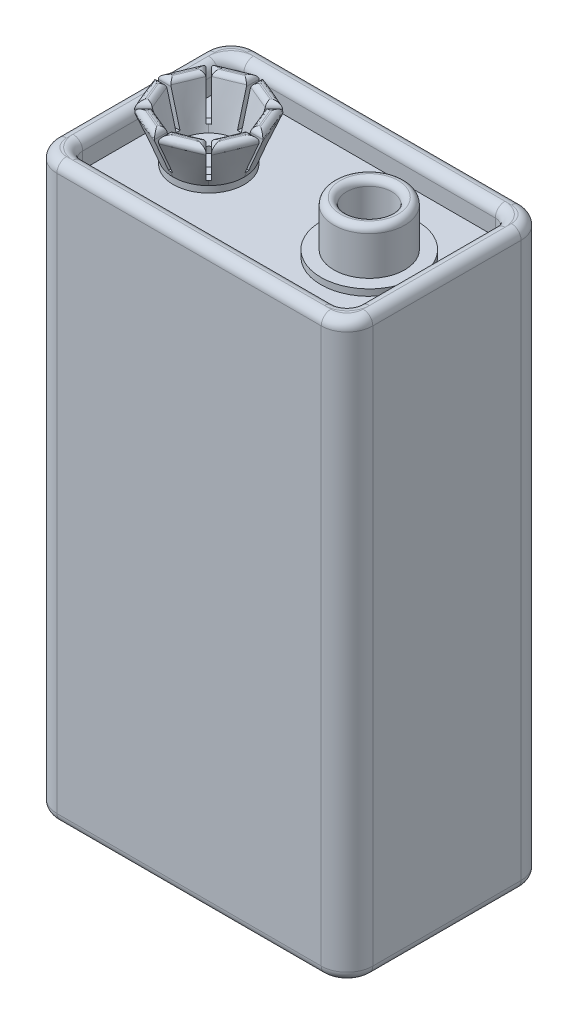
SolidWorks part; units mm, degrees
ref_plane "Front Plane" through (0, 0, 0) normal (0, 0, 1) x (1, 0, 0)
ref_plane "Top Plane" through (0, 0, 0) normal (0, 1, 0) x (1, 0, 0)
ref_plane "Right Plane" through (0, 0, 0) normal (1, 0, 0) x (0, 0, -1)
sketch "Sketch1" plane through (0, 0, 0) normal (0, 1, 0) x (1, 0, 0)
  line L1 (-10.25, -7.75) -> (10.25, -7.75)
  line L2 (-12.25, -5.75) -> (-12.25, 5.75)
  line L3 (-10.25, 7.75) -> (10.25, 7.75)
  line L4 (12.25, -5.75) -> (12.25, 5.75)
  line L5 (-12.25, -7.75) -> (12.25, 7.75) construction
  line L6 (-12.25, 7.75) -> (12.25, -7.75) construction
  arc A0 (10.25, -7.75) -> (12.25, -5.75) centre (10.25, -5.75) ccw
  arc A1 (-10.25, -7.75) -> (-12.25, -5.75) centre (-10.25, -5.75) cw
  arc A2 (10.25, 7.75) -> (12.25, 5.75) centre (10.25, 5.75) cw
  arc A3 (-12.25, 5.75) -> (-10.25, 7.75) centre (-10.25, 5.75) cw
  point P0 (0, 0)
  dimension "D3" = 2
  dimension "D1" = 24.5
  dimension "D2" = 15.5
extrude "Boss-Extrude1" add sketch "Sketch1" along normal blind 44.5
sketch "Sketch2" plane through (0, 0, 0) normal (0, -1, 0) x (-1, 0, 0)
  line L0 (10.25, -7.75) -> (-10.25, -7.75) construction
  line L1 (9.25, 6.25) -> (-9.25, 6.25)
  line L2 (10.75, 4.75) -> (10.75, -4.75)
  line L3 (9.25, -6.25) -> (-9.25, -6.25)
  line L4 (-10.75, 4.75) -> (-10.75, -4.75)
  line L5 (10.75, 6.25) -> (-10.75, -6.25) construction
  line L6 (10.75, -6.25) -> (-10.75, 6.25) construction
  line L7 (-12.25, -5.75) -> (-12.25, 5.75) construction
  arc A0 (-9.25, 6.25) -> (-10.75, 4.75) centre (-9.25, 4.75) ccw
  arc A1 (9.25, 6.25) -> (10.75, 4.75) centre (9.25, 4.75) cw
  arc A2 (-9.25, -6.25) -> (-10.75, -4.75) centre (-9.25, -4.75) cw
  arc A3 (10.75, -4.75) -> (9.25, -6.25) centre (9.25, -4.75) cw
  point P0 (0, 0)
  dimension "D3" = 1.5
  dimension "D1" = 1.5
  dimension "D2" = 1.5
extrude "Cut-Extrude1" cut sketch "Sketch2" against normal blind 2
fillet "Fillet1" radius 0.75 16 edges at (12.25, 0, 0) (11.6642, 0, -7.1642) (0, 0, -7.75) (-11.6642, 0, -7.1642) (-12.25, 0, 0) (-11.6642, 0, 7.1642) (0, 0, 7.75) (11.6642, 0, 7.1642) (10.3107, 0, 5.8107) (0, 0, 6.25) (-10.3107, 0, 5.8107) (-10.75, 0, 0) (-10.3107, 0, -5.8107) (0, 0, -6.25) (10.3107, 0, -5.8107) (10.75, 0, 0)
sketch "Sketch3" plane through (0, 2, 0) normal (0, -1, 0) x (-1, 0, 0)
  line L1 (9, 5.5) -> (-9, 5.5)
  line L2 (10, 4.5) -> (10, -4.5)
  line L3 (9, -5.5) -> (-9, -5.5)
  line L4 (-10, 4.5) -> (-10, -4.5)
  line L5 (10, 5.5) -> (-10, -5.5) construction
  line L6 (10, -5.5) -> (-10, 5.5) construction
  arc A0 (-9, 5.5) -> (-10, 4.5) centre (-9, 4.5) ccw
  arc A1 (9, 5.5) -> (10, 4.5) centre (9, 4.5) cw
  arc A2 (-9, -5.5) -> (-10, -4.5) centre (-9, -4.5) cw
  arc A3 (10, -4.5) -> (9, -5.5) centre (9, -4.5) cw
  point P0 (0, 0)
  dimension "D3" = 1
  dimension "D1" = 20
  dimension "D2" = 11
extrude "Boss-Extrude2" add sketch "Sketch3" along normal blind 1
fillet "Fillet2" radius 0.5 16 edges at (0, 1, -5.5) (-9.7071, 1, -5.2071) (-10, 1, 0) (-9.7071, 1, 5.2071) (0, 1, 5.5) (9.7071, 1, 5.2071) (10, 1, 0) (9.7071, 1, -5.2071) (-10, 2, 0) (-9.7071, 2, 5.2071) (0, 2, 5.5) (9.7071, 2, 5.2071) (10, 2, 0) (9.7071, 2, -5.2071) (0, 2, -5.5) (-9.7071, 2, -5.2071)
sketch "Sketch4" plane through (0, 44.5, 0) normal (0, 1, 0) x (1, 0, 0)
  line L1 (10.25, 7.75) -> (-10.25, 7.75) construction
  line L2 (-9.75, -6.25) -> (9.75, -6.25)
  line L3 (-10.75, -5.25) -> (-10.75, 5.25)
  line L4 (-9.75, 6.25) -> (9.75, 6.25)
  line L5 (10.75, -5.25) -> (10.75, 5.25)
  line L6 (-10.75, -6.25) -> (10.75, 6.25) construction
  line L8 (-10.75, 6.25) -> (10.75, -6.25) construction
  line L9 (12.25, -5.75) -> (12.25, 5.75) construction
  arc A0 (9.75, -6.25) -> (10.75, -5.25) centre (9.75, -5.25) ccw
  arc A1 (-9.75, -6.25) -> (-10.75, -5.25) centre (-9.75, -5.25) cw
  arc A2 (9.75, 6.25) -> (10.75, 5.25) centre (9.75, 5.25) cw
  arc A3 (-10.75, 5.25) -> (-9.75, 6.25) centre (-9.75, 5.25) cw
  point P0 (0, 0)
  dimension "D3" = 1
  dimension "D1" = 1.5
  dimension "D2" = 1.5
extrude "Cut-Extrude2" cut sketch "Sketch4" against normal blind 2
fillet "Fillet4" radius 0.75 16 edges at (0, 44.5, 7.75) (-11.6642, 44.5, 7.1642) (-12.25, 44.5, 0) (-11.6642, 44.5, -7.1642) (0, 44.5, -7.75) (11.6642, 44.5, -7.1642) (12.25, 44.5, 0) (11.6642, 44.5, 7.1642) (10.75, 44.5, 0) (10.4571, 44.5, -5.9571) (0, 44.5, -6.25) (-10.4571, 44.5, -5.9571) (-10.75, 44.5, 0) (-10.4571, 44.5, 5.9571) (0, 44.5, 6.25) (10.4571, 44.5, 5.9571)
sketch "Sketch5" plane through (0, 42.5, 0) normal (0, 1, 0) x (1, 0, 0)
  circle A1 centre (6.225, 0) radius 3.75
extrude "Boss-Extrude3" add sketch "Sketch5" along normal blind 0.5
sketch "Sketch6" plane through (0, 43, 0) normal (0, 1, 0) x (1, 0, 0)
  circle A0 centre (6.225, 0) radius 2.75
  circle A1 centre (6.225, 0) radius 1.75
  dimension "D1" = 5.5
  dimension "D4" = 3.5
  dimension "D2" = 6.225
  dimension "D3" = 0
extrude "Boss-Extrude4" add sketch "Sketch6" along normal blind 3.5
sketch "Sketch7" plane through (0, 43, 0) normal (0, 1, 0) x (1, 0, 0)
  circle A0 centre (6.225, 0) radius 1
  dimension "D1" = 6.225
  dimension "D3" = 2
  dimension "D2" = 0
extrude "Cut-Extrude3" cut sketch "Sketch7" against normal blind 0.5
fillet "Fillet6" radius 0.5 2 edges at (6.225, 46.5, 1.75) (6.225, 46.5, 2.75)
sketch "Sketch8" plane through (0, 42.5, 0) normal (0, 1, 0) x (1, 0, 0)
  circle A0 centre (-6.225, 0) radius 2.75
  dimension "D1" = 5.5
  dimension "D2" = 6.225
  dimension "D3" = 0
extrude "Boss-Extrude5" add sketch "Sketch8" along normal blind 0.5
ref_plane "Plane1" through (0, 46.5, 0) normal (0, 1, 0) x (1, 0, 0)
sketch "Sketch9" plane through (0, 46.5, 0) normal (0, 1, 0) x (1, 0, 0)
  line L1 (-3.1523, 3.0502) -> (-6.209, 4.3295)
  line L2 (-6.209, 4.3295) -> (-9.2752, 3.0727)
  line L3 (-9.2752, 3.0727) -> (-10.5545, 0.016)
  line L4 (-10.5545, 0.016) -> (-9.2977, -3.0502)
  line L5 (-9.2977, -3.0502) -> (-6.241, -4.3295)
  line L6 (-6.241, -4.3295) -> (-3.1748, -3.0727)
  line L7 (-3.1748, -3.0727) -> (-1.8955, -0.016)
  line L8 (-1.8955, -0.016) -> (-3.1523, 3.0502)
  circle A0 centre (-6.225, 0) radius 4 construction
  dimension "D1" = 8
  dimension "D2" = 6.225
sketch "Sketch11" plane through (0, 43, 0) normal (0, 1, 0) x (1, 0, 0)
  circle A0 centre (-6.225, 0) radius 2.75
  dimension "D1" = 5.5
  dimension "D2" = 6.225
  dimension "D3" = 0
loft "Loft1" add profiles "Sketch11", "Sketch9"
sketch "Sketch12" plane through (0, 43, 0) normal (0, 1, 0) x (1, 0, 0)
  circle A0 centre (-6.225, 0) radius 2.25
  dimension "D1" = 4.5
sketch "Sketch14" plane through (0, 46.5, 0) normal (0, 1, 0) x (1, 0, 0)
  line L1 (-2.9778, 0) -> (-3.9289, 2.2961)
  line L2 (-3.9289, 2.2961) -> (-6.225, 3.2472)
  line L3 (-6.225, 3.2472) -> (-8.5211, 2.2961)
  line L4 (-8.5211, 2.2961) -> (-9.4722, 0)
  line L5 (-9.4722, 0) -> (-8.5211, -2.2961)
  line L6 (-8.5211, -2.2961) -> (-6.225, -3.2472)
  line L7 (-6.225, -3.2472) -> (-3.9289, -2.2961)
  line L8 (-3.9289, -2.2961) -> (-2.9778, 0)
  circle A0 centre (-6.225, 0) radius 3 construction
  dimension "D1" = 6
loft "Cut-Loft1" cut profiles "Sketch12", "Sketch14"
sketch "Sketch16" plane through (0, 46.5, 0) normal (0, 1, 0) x (1, 0, 0)
  line L2 (-6.375, -4.5) -> (-6.075, -4.5)
  line L3 (-6.375, -4.5) -> (-6.375, 4.5)
  line L5 (-6.375, 4.5) -> (-6.075, 4.5)
  line L6 (-6.075, -4.5) -> (-6.075, 4.5)
  line L8 (-6.375, -4.5) -> (-6.075, 4.5) construction
  line L10 (-6.375, 4.5) -> (-6.075, -4.5) construction
  point P0 (-6.225, 0)
  dimension "D1" = 0.3
  dimension "D2" = 6.225
  dimension "D3" = 9
extrude "Cut-Extrude4" cut sketch "Sketch16" against normal blind 3
ref_axis "Axis1" through (-6.225, 43.1562, 0) along (0, -1, 0)
pattern_circular "CirPattern1" count 8 over 360 about axis through (-6.225, 43.1562, 0) along (0, -1, 0) of "Cut-Extrude4"
fillet "Fillet7" radius 0.4 32 edges
sketch "Sketch19" plane through (0, 43, 0) normal (0, 1, 0) x (1, 0, 0)
  circle A0 centre (-6.225, 0) radius 1
  dimension "D1" = 2
extrude "Cut-Extrude5" cut sketch "Sketch19" against normal blind 0.5 contours A0
